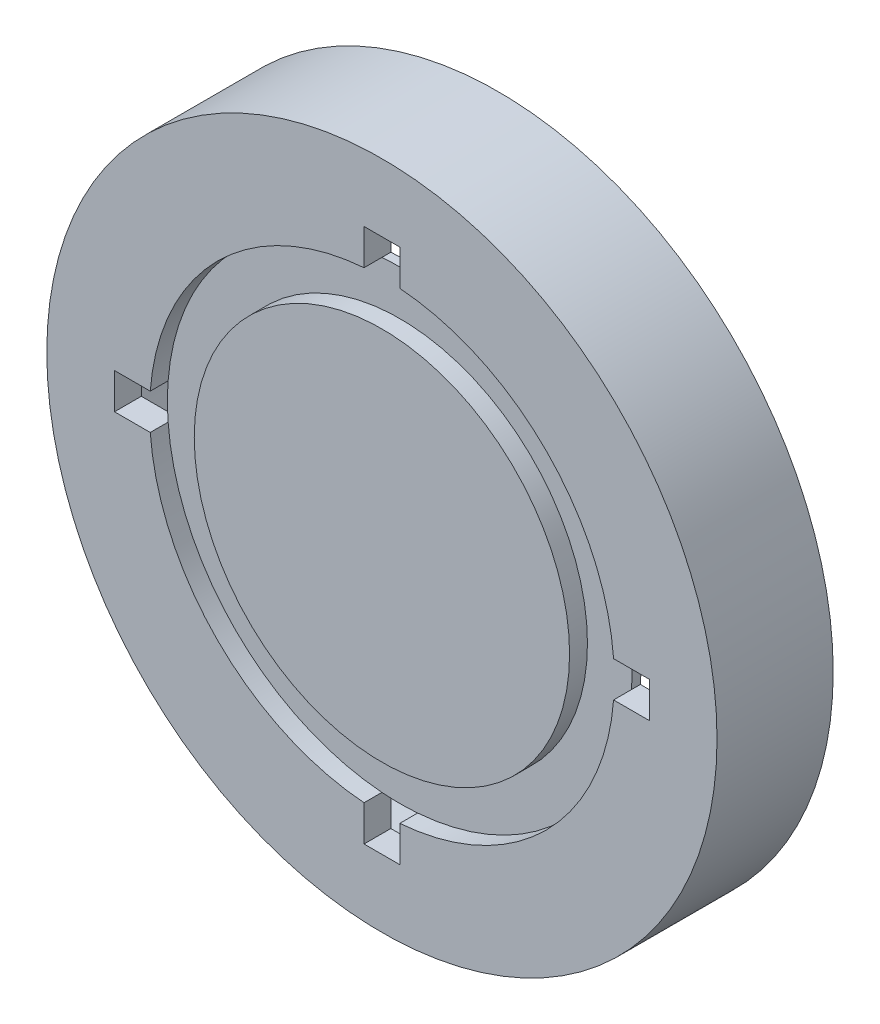
SolidWorks part; units mm, degrees
ref_plane "Front Plane" through (0, 0, 0) normal (0, 0, 1) x (1, 0, 0)
ref_plane "Top Plane" through (0, 0, 0) normal (0, 1, 0) x (1, 0, 0)
ref_plane "Right Plane" through (0, 0, 0) normal (1, 0, 0) x (0, 0, -1)
sketch "Sketch1" plane through (0, 0, 0) normal (0, 0, 1) x (1, 0, 0)
  circle A0 centre (0, 0) radius 47.625
  dimension "D1" = 95.25
extrude "Boss-Extrude1" add sketch "Sketch1" along normal blind 3.81
sketch "Sketch2" plane through (0, 0, 3.81) normal (0, 0, 1) x (1, 0, 0)
  circle A0 centre (0, 0) radius 33.02
  circle A1 centre (0, 0) radius 26.67
  dimension "D1" = 66.04
  dimension "D2" = 53.34
extrude "Cut-Extrude1" cut sketch "Sketch2" against normal blind 2.54
sketch "Sketch3" plane through (0, 0, 3.81) normal (0, 0, 1) x (1, 0, 0)
  line L0 (0, 33.02) -> (0, -33.02) construction
  line L1 (32.9222, -2.54) -> (38.0022, -2.54)
  line L2 (32.9222, -2.54) -> (32.9222, 2.54)
  line L3 (32.9222, 2.54) -> (38.0022, 2.54)
  line L4 (38.0022, -2.54) -> (38.0022, 2.54)
  line L5 (-33.02, 0) -> (32.9222, 0) construction
  line L6 (-32.9222, -2.54) -> (-32.9222, 2.54)
  line L7 (-32.9222, -2.54) -> (-38.0022, -2.54)
  line L8 (-38.0022, -2.54) -> (-38.0022, 2.54)
  line L9 (-32.9222, 2.54) -> (-38.0022, 2.54)
  line L10 (0, 38.0022) -> (0, 32.9222)
  line L11 (-2.54, 38.0022) -> (2.54, 38.0022)
  line L12 (-2.54, 38.0022) -> (-2.54, 32.9222)
  line L13 (-2.54, 32.9222) -> (2.54, 32.9222)
  line L14 (2.54, 38.0022) -> (2.54, 32.9222)
  line L15 (-2.54, -32.9222) -> (2.54, -32.9222)
  line L16 (-2.54, -38.0022) -> (-2.54, -32.9222)
  line L17 (2.54, -38.0022) -> (2.54, -32.9222)
  line L18 (-2.54, -38.0022) -> (2.54, -38.0022)
  circle A0 centre (0, 0) radius 33.02 construction
  circle A1 centre (0, 0) radius 33.02 construction
  circle M4 centre (0, 0) radius 33.02
  dimension "D1" = 5.08
  dimension "D2" = 5.08
  dimension "D3" = 5.08
  dimension "D5" = 0
extrude "Cut-Extrude2" cut sketch "Sketch3" against normal through all contours L14 L11 L10 M4 | L11 L12 L10 M4 | L9 L8 L7 M4 | L16 L18 L17 M4 | L1 L4 L3 M4 region at (35.4947, 0, 3.81) region at (0, -35.4947, 3.81) region at (1.2741, 35.4947, 3.81) region at (-1.2741, 35.4947, 3.81) region at (-35.4947, 0, 3.81)
sketch "Sketch4" plane through (0, 0, 0) normal (0, 0, -1) x (-1, 0, 0)
  circle A0 centre (0, 0) radius 47.625
  circle A1 centre (0, 0) radius 44.45
  dimension "D1" = 88.9
extrude "Boss-Extrude2" add sketch "Sketch4" along normal blind 12.7
equation "\"D1@Boss-Extrude1\"=0.15"
